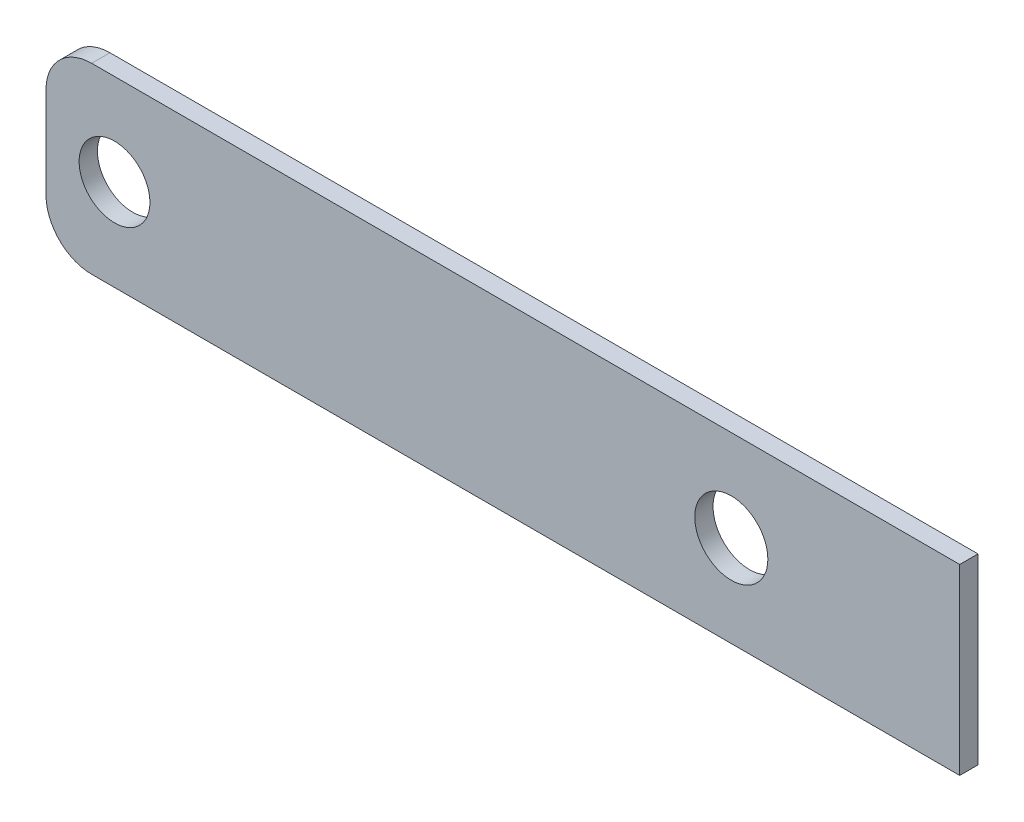
SolidWorks part; units mm, degrees
material "1.4003 (X2CrNi12)"
ref_plane "Ön Düzlem" through (0, 0, 0) normal (0, 0, 1) x (1, 0, 0)
ref_plane "Üst Düzlem" through (0, 0, 0) normal (0, 1, 0) x (1, 0, 0)
ref_plane "Sağ Düzlem" through (0, 0, 0) normal (1, 0, 0) x (0, 0, -1)
sketch "Çizim1" plane through (0, 0, 0) normal (0, 0, 1) x (1, 0, 0)
  line L1 (-100, 20) -> (100, 20)
  line L2 (-100, 20) -> (-100, -20)
  line L3 (-100, -20) -> (100, -20)
  line L4 (100, 20) -> (100, -20)
  line L5 (-100, 20) -> (100, -20) construction
  line L6 (-100, -20) -> (100, 20) construction
  point P0 (0, 0)
  dimension "D1" = 40
  dimension "D2" = 200
base flange "Taban-Flanş1" sketch "Çizim1" thickness 4 reverse thickness direction no parameters "D1"=2
sketch "Çizim6" plane through (0, 0, 0) normal (0, 0, 1) x (1, 0, 0)
  line L0 (-100, 20) -> (-100, -20) construction
  line L1 (100, 20) -> (-100, 20) construction
  line L2 (100, -20) -> (100, 20) construction
  circle A0 centre (-85, 0) radius 7.75
  circle A1 centre (50, 0) radius 8
  dimension "D1" = 15.5
  dimension "D3" = 20
  dimension "D4" = 16
  dimension "D5" = 50
  dimension "D6" = 20
  dimension "D2" = 15
extrude "Kes-Ekstrüzyon1" cut sketch "Çizim6" against normal blind 10
fillet "Radyus1" radius 10 2 edges at (-100, -20, -2) (-100, 20, -2)
sketch "Büküm-Çizgileri1" [suppressed] plane through (0, 0, 0) normal (0, 1, 0) x (1, 0, 0)
sketch "Sınırlandırma-Kutusu1" [suppressed] plane through (0, 0, 0) normal (0, 1, 0) x (1, 0, 0)
sheet metal parameters "Sac-Levha1" thickness 4 parameters "D1"=2
flat pattern "Düz-Çoğaltma1" [suppressed]
sketch "Büküm-Çizgileri2" plane through (0, 0, 0) normal (0, 1, 0) x (1, 0, 0)
sketch3d "Sınırlandırma-Kutusu2" [suppressed]
  line L0 (100, -20, 0) -> (-100, -20, 0) construction
  line L1 (100, 20, 0) -> (-100, 20, 0) construction
  line L2 (100, -20, 0) -> (100, 20, 0) construction
  line L3 (-100, -20, 0) -> (-100, 20, 0) construction
sheet metal parameters "Sac-Levha2" thickness 4 parameters "D1"=2
flat pattern "Düz-Çoğaltma1"
sketch "Büküm-Çizgileri2" plane through (0, 0, 0) normal (0, 1, 0) x (1, 0, 0)
sketch3d "Sınırlandırma-Kutusu2" [suppressed]
  line L0 (-100, -20, 0) -> (100, -20, 0) construction
  line L1 (-100, 20, 0) -> (100, 20, 0) construction
  line L2 (-100, -20, 0) -> (-100, 20, 0) construction
  line L3 (100, -20, 0) -> (100, 20, 0) construction
